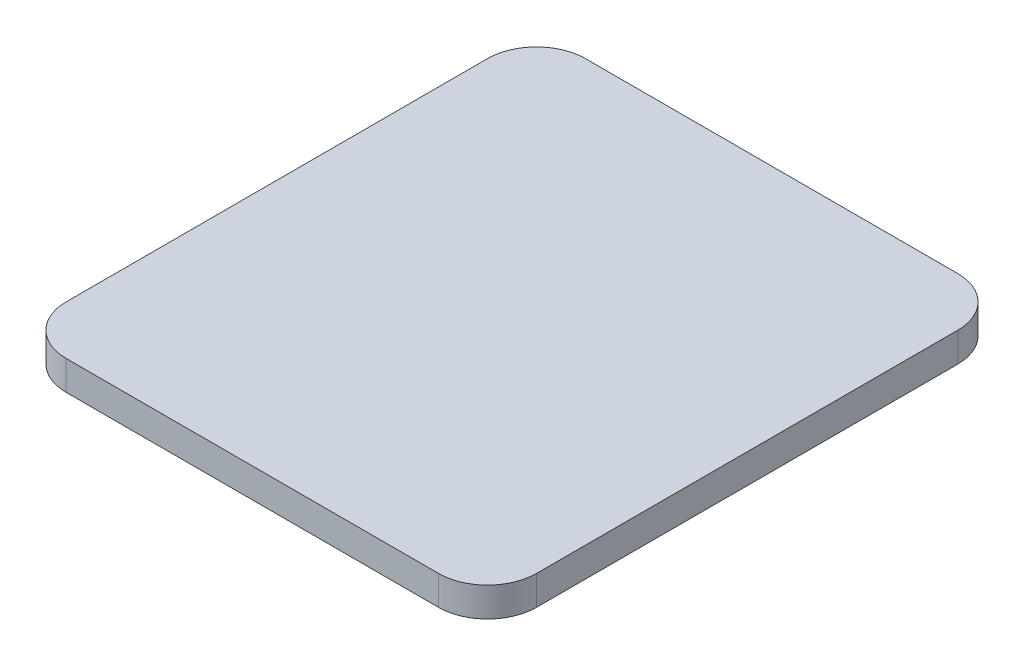
SolidWorks part; units mm, degrees
ref_plane "Front Plane" through (0, 0, 0) normal (0, 0, 1) x (1, 0, 0)
ref_plane "Top Plane" through (0, 0, 0) normal (0, 1, 0) x (1, 0, 0)
ref_plane "Right Plane" through (0, 0, 0) normal (1, 0, 0) x (0, 0, -1)
sketch "Sketch1" plane through (0, 24.6718, 0) normal (0, -1, 0) x (1, 0, 0)
  line L8 (13.9215, 29.7805) -> (51.9215, 29.7805)
  line L9 (56.9215, 34.7805) -> (56.9215, 77.7805)
  line L10 (51.9215, 82.7805) -> (13.9215, 82.7805)
  line L11 (8.9215, 77.7805) -> (8.9215, 34.7805)
  line L12 (13.9215, 29.7805) -> (51.9215, 29.7805)
  line L13 (56.9215, 34.7805) -> (56.9215, 77.7805)
  line L14 (51.9215, 82.7805) -> (13.9215, 82.7805)
  line L15 (8.9215, 77.7805) -> (8.9215, 34.7805)
  arc A8 (8.9215, 34.7805) -> (13.9215, 29.7805) centre (13.9215, 34.7805) ccw
  arc A9 (51.9215, 29.7805) -> (56.9215, 34.7805) centre (51.9215, 34.7805) ccw
  arc A10 (56.9215, 77.7805) -> (51.9215, 82.7805) centre (51.9215, 77.7805) ccw
  arc A11 (13.9215, 82.7805) -> (8.9215, 77.7805) centre (13.9215, 77.7805) ccw
  arc A12 (8.9215, 34.7805) -> (13.9215, 29.7805) centre (13.9215, 34.7805) ccw
  arc A13 (51.9215, 29.7805) -> (56.9215, 34.7805) centre (51.9215, 34.7805) ccw
  arc A14 (56.9215, 77.7805) -> (51.9215, 82.7805) centre (51.9215, 77.7805) ccw
  arc A15 (13.9215, 82.7805) -> (8.9215, 77.7805) centre (13.9215, 77.7805) ccw
  dimension "D1" = 0
extrude "Boss-Extrude1" add sketch "Sketch1" along normal blind 3
